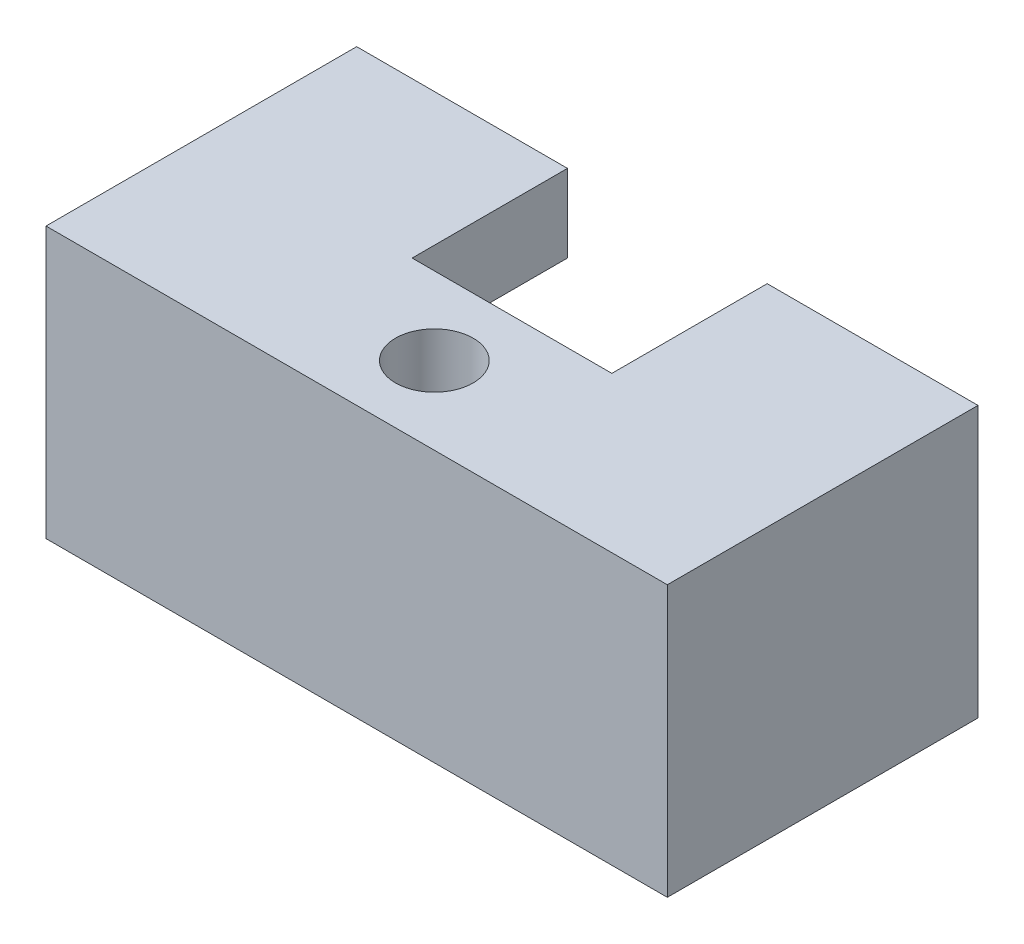
SolidWorks part; units mm, degrees
ref_plane "Front Plane" through (0, 0, 0) normal (0, 0, 1) x (1, 0, 0)
ref_plane "Top Plane" through (0, 0, 0) normal (0, 1, 0) x (1, 0, 0)
ref_plane "Right Plane" through (0, 0, 0) normal (1, 0, 0) x (0, 0, -1)
sketch "Sketch1" plane through (0, 0, 0) normal (0, 1, 0) x (1, 0, 0)
  line L0 (-14, 7) -> (-4.5, 7)
  line L1 (-4.5, 7) -> (-4.5, 0)
  line L2 (-4.5, 0) -> (4.5, 0)
  line L3 (4.5, 0) -> (4.5, 7)
  line L4 (4.5, 7) -> (14, 7)
  line L5 (14, 7) -> (14, -7)
  line L6 (14, -7) -> (-14, -7)
  line L7 (-14, -7) -> (-14, 7)
  line L8 (-9.25, 7) -> (-9.25, 0)
  line L9 (-9.25, 0) -> (-4.5, 0)
  line L10 (4.5, 0) -> (9.25, 0)
  line L11 (9.25, 0) -> (9.25, 7)
  line L12 (0, 0) -> (0, -7) construction
  circle A0 centre (0, -3.5) radius 1.75
  point P14 (0, 0)
  point P16 (14, 0)
  point P19 (0, -3.5)
  dimension "D6" = 3.5
  dimension "D1" = 9
  dimension "D2" = 18.5
  dimension "D3" = 28
  dimension "D4" = 7
  dimension "D5" = 14
extrude "Boss-Extrude1" add sketch "Sketch1" along normal blind 8.7 contours L12 L2 L9 L8 L0 L7 L6 A0 | L2 L12 A0 L6 L5 L4 L11 L10 region at (-8.4543, 0, 1.6592) region at (8.4543, 0, 1.6592)
extrude "Boss-Extrude2" add sketch "Sketch1<3>" along normal blind 3.5 from surface contours L8 L9 L1 L0 | L12 L2 L9 L8 L0 L7 L6 A0 | L10 L11 L4 L3 | L2 L12 A0 L6 L5 L4 L11 L10 region at (-8.4543, 0, 1.6592) region at (-6.875, 0, -3.5) region at (8.4543, 0, 1.6592) region at (6.875, 0, -3.5) starting at face at (0, 8.7, 5.25)
sketch "Sketch1<3>" plane through (0, 0, 0) normal (0, 1, 0) x (1, 0, 0) same geometry as "Sketch1"
